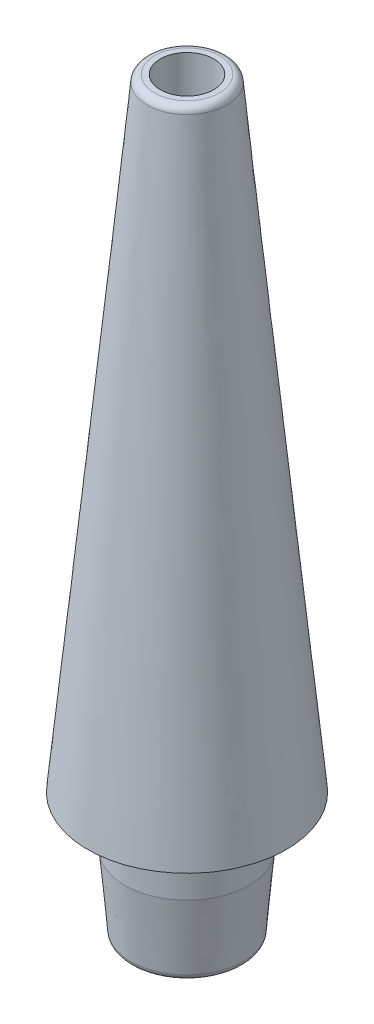
SolidWorks part; units mm, degrees
material "ABS"
ref_plane "Front Plane" through (0, 0, 0) normal (0, 0, 1) x (1, 0, 0)
ref_plane "Top Plane" through (0, 0, 0) normal (0, 1, 0) x (1, 0, 0)
ref_plane "Right Plane" through (0, 0, 0) normal (1, 0, 0) x (0, 0, -1)
sketch "Sketch1" plane through (0, 0, 0) normal (0, 1, 0) x (1, 0, 0)
  circle A0 centre (0, 0) radius 2.5
  dimension "D1" = 5
extrude "Boss-Extrude1" add sketch "Sketch1" along normal blind 5
sketch "Sketch2" plane through (0, 5, 0) normal (0, 1, 0) x (1, 0, 0)
  circle A0 centre (0, 0) radius 4
  dimension "D1" = 8
ref_plane "Plane1" through (0, 30, 0) normal (0, 1, 0) x (1, 0, 0)
sketch "Sketch3" plane through (0, 30, 0) normal (0, 1, 0) x (1, 0, 0)
  circle A0 centre (0, 0) radius 1.575
  circle A1 centre (0, 0) radius 1.075 construction
  dimension "D1" = 0.5
  dimension "D2" = 2.15
loft "Loft1" add profiles "Sketch3", "Sketch2" connector at (-1.3924, 30, -0.7361) connector at (-3.844, 5, -1.1063)
sketch "Sketch4" plane through (0, 30, 0) normal (0, 1, 0) x (1, 0, 0)
  circle A0 centre (0, 0) radius 1.075
  dimension "D1" = 2.15
extrude "Cut-Extrude1" cut sketch "Sketch4" against normal through all
chamfer "Chamfer1" distance 0.3 angle 89 1 edges at (0, 0, 1.075) first distance on face at (0, 0, 1.075)
chamfer "Chamfer2" distance 3 angle 5 1 edges at (0, 0, 2.5) first distance on face at (0, 5, 2.5)
fillet "Fillet1" radius 0.3 1 edges at (0, 30, 1.575)
fillet "Fillet2" radius 0.25 1 edges at (0, 5, 2.5)
fillet "Fillet4" radius 0.25 2 edges at (0, 0, 1.375) (0, 0, 2.2375)
